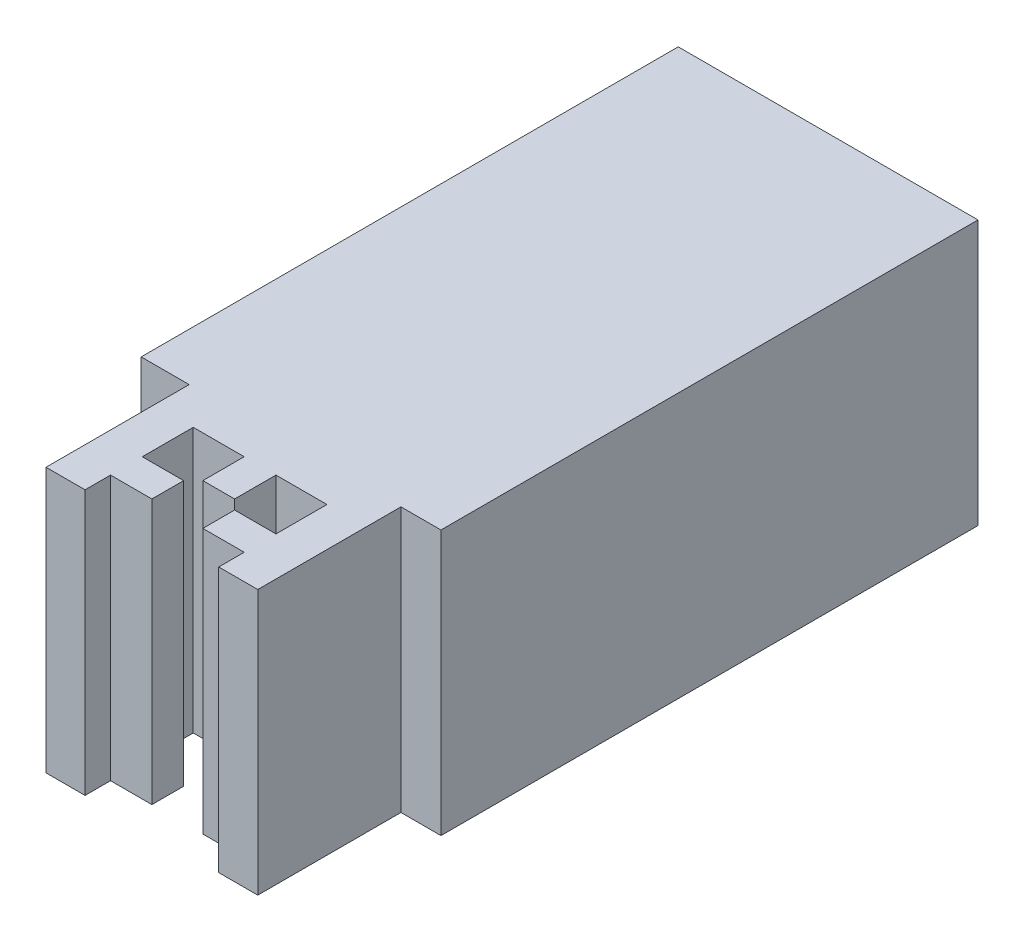
SolidWorks part; units mm, degrees
ref_plane "Plan de face" through (0, 0, 0) normal (0, 0, 1) x (1, 0, 0)
ref_plane "Plan de dessus" through (0, 0, 0) normal (0, 1, 0) x (1, 0, 0)
ref_plane "Plan de droite" through (0, 0, 0) normal (1, 0, 0) x (0, 0, -1)
sketch "Base" plane through (0, 0, 0) normal (0, 1, 0) x (1, 0, 0)
  line L0 (-3.85, -2.4) -> (-3.85, 2.4)
  line L1 (-3.85, 2.4) -> (-10.1, 2.4)
  line L2 (-10.1, 2.4) -> (-10.1, 10.1)
  line L3 (-10.1, 10.1) -> (-2.4, 10.1)
  line L4 (-2.4, 10.1) -> (-2.4, 3.85)
  line L5 (-2.4, 3.85) -> (2.4, 3.85)
  line L6 (0, -16.94) -> (0, 16.94) construction
  line L7 (2.4, 10.1) -> (2.4, 3.85)
  line L8 (10.1, 10.1) -> (2.4, 10.1)
  line L9 (10.1, 2.4) -> (10.1, 10.1)
  line L10 (3.85, 2.4) -> (10.1, 2.4)
  line L11 (3.85, -2.4) -> (3.85, 2.4)
  line L12 (-16.94, 0) -> (16.94, 0) construction
  line L13 (3.85, -2.4) -> (10.1, -2.4)
  line L14 (10.1, -2.4) -> (10.1, -6.25)
  line L20 (-10.1, -2.4) -> (-10.1, -6.25)
  line L21 (-3.85, -2.4) -> (-10.1, -2.4)
  line L23 (-15.4, 15.4) -> (15.4, 15.4)
  line L24 (-15.4, 15.4) -> (-15.4, -6.25)
  line L26 (15.4, 15.4) -> (15.4, -6.25)
  line L27 (-15.4, 15.4) -> (0, 0) construction
  line L28 (0, 0) -> (15.4, 15.4) construction
  line L29 (-10.1, -6.25) -> (-15.4, -6.25)
  line L30 (10.1, -6.25) -> (15.4, -6.25)
  line L31 (10.1, -10.1) -> (15.4, -15.4) construction
  point P2 (-3.85, 0)
  point P3 (0, 3.85)
  point P27 (0, 0)
  dimension "D1" = 4.8
  dimension "D2" = 4.8
  dimension "D3" = 6.25
  dimension "D4" = 7.7
  dimension "D5" = 30.8
extrude "Boss.-Extru.1" add sketch "Base" along normal mid plane 40
sketch "Esquisse6" plane through (0, 0, 0) normal (0, 0, 1) x (1, 0, 0)
  line L0 (10.1, 20) -> (10.1, -20) construction
  line L1 (-10.1, 10) -> (10.1, 10)
  line L2 (-10.1, 10) -> (-10.1, -10)
  line L3 (-10.1, -10) -> (10.1, -10)
  line L4 (10.1, 10) -> (10.1, -10)
  line L5 (-10.1, 10) -> (10.1, -10) construction
  line L6 (-10.1, -10) -> (10.1, 10) construction
  point P0 (0, 0)
  dimension "D1" = 20
extrude "Enlèv. mat.-Extru.1" cut sketch "Esquisse6" against normal mid plane 6
sketch "Esquisse14" plane through (0, -20, 0) normal (0, -1, 0) x (1, 0, 0)
  line L0 (15.4, 6.25) -> (15.4, -15.4) construction
  line L1 (-15.4, -15.4) -> (15.4, -15.4)
  line L2 (-15.4, -15.4) -> (-15.4, -17.9)
  line L3 (-15.4, -17.9) -> (15.4, -17.9)
  line L4 (15.4, -15.4) -> (15.4, -17.9)
  dimension "D1" = 2.5
extrude "Boss.-Extru.3" add sketch "Esquisse14" against normal up to vertex (40 mm away)
chamfer "Chanfrein1" distance 6.25 angle 45 2 edges at (3.85, -10, 0) (-3.85, -10, 0)
sketch "Esquisse16" plane through (15.4, 0, 0) normal (1, 0, 0) x (0, 0, -1)
  line L0 (-6.25, -20) -> (17.9, -20) construction
  line L1 (-6.25, 20) -> (17.9, 20)
  line L2 (-6.25, 20) -> (-6.25, -20)
  line L3 (-6.25, -20) -> (17.9, -20)
  line L4 (17.9, 20) -> (17.9, -20)
  line L5 (17.9, 20) -> (17.9, -20) construction
  line L6 (-6.25, 20) -> (-6.25, -20) construction
  dimension "D1" = 0
  dimension "D2" = 0
  dimension "D3" = 0
  dimension "D4" = 0
extrude "Boss.-Extru.4" add sketch "Esquisse16" along normal blind 40
sketch "Esquisse17" plane through (0, 0, -17.9) normal (0, 0, -1) x (-1, 0, 0)
  line L0 (15.4, 20) -> (-55.4, 20) construction
  circle A0 centre (-34.1338, 0) radius 17.5
  dimension "D1" = 20
sketch "Esquisse18" plane through (0, 0, 6.25) normal (0, 0, 1) x (1, 0, 0)
  line L0 (10.1, 20) -> (55.4, 20) construction
  line L1 (10.1, 20) -> (55.4, 20)
  line L2 (10.1, 20) -> (10.1, -20)
  line L3 (10.1, -20) -> (55.4, -20)
  line L4 (55.4, 20) -> (55.4, -20)
  line L5 (55.4, 20) -> (55.4, -20) construction
  line L6 (10.1, -20) -> (55.4, -20) construction
  line L7 (10.1, 20) -> (10.1, -20) construction
  dimension "D1" = 0
  dimension "D2" = 0
  dimension "D3" = 0
  dimension "D4" = 0
extrude "Boss.-Extru.5" add sketch "Esquisse18" along normal blind 47
extrude "Enlèv. mat.-Extru.4" cut sketch "Esquisse17" against normal blind 86
sketch "Esquisse19" plane through (0, -20, 0) normal (0, -1, 0) x (-1, 0, 0)
  line L0 (-10.1, -2.4) -> (-10.1, -53.25) construction
  line L1 (-29.1, -53.25) -> (-39.1, -53.25)
  line L2 (-29.1, -53.25) -> (-29.1, 19.3245)
  line L3 (-29.1, 19.3245) -> (-39.1, 19.3245)
  line L4 (-39.1, -53.25) -> (-39.1, 19.3245)
  line L5 (-10.1, -53.25) -> (-55.4, -53.25) construction
  dimension "D2" = 10
  dimension "D3" = 19
  dimension "D4" = 0
extrude "Enlèv. mat.-Extru.5" cut sketch "Esquisse19" against normal blind 6
sketch "Esquisse22" plane through (10.1, 0, 0) normal (-1, 0, 0) x (0, 0, 1)
  line L0 (2.4, 20) -> (53.25, 20) construction
  circle A0 centre (39.6977, 0) radius 4
  dimension "D1" = 20
extrude "Enlèv. mat.-Extru.6" cut sketch "Esquisse22" against normal blind 1 contours A0
sketch "Esquisse23" plane through (11.1, 0, 0) normal (-1, 0, 0) x (0, 0, 1)
  circle A0 centre (39.6977, 0) radius 1.25
  circle A2 centre (39.6977, 0) radius 4 construction
  dimension "D1" = 0
extrude "Enlèv. mat.-Extru.7" cut sketch "Esquisse23" against normal blind 7 contours A0
chamfer "Chanfrein4" distance 0.25 angle 45 1 edges at (11.1, 0, 40.9477)
sketch "Esquisse54" plane through (10.1, 0, 0) normal (-1, 0, 0) x (0, 0, 1)
  circle A0 centre (39.6977, 0) radius 1.6
curve "Hélice/Spirale1" pitch 0.5 height 10 turns 20
sketch "Esquisse55" plane through (0, 0, 0) normal (0, 1, 0) x (1, 0, 0)
  line L0 (14.9838, -38.4485) -> (14.5912, -38.4485)
  line L1 (14.5912, -38.4485) -> (14.7847, -38.1985)
  line L2 (14.7847, -38.1985) -> (14.9838, -38.4485)
  line L3 (14.7847, -38.1985) -> (14.7847, -38.4485)
  spline S0 degree 3 poles (10.1, -38.5663) (10.1104, -38.7135) (10.1313, -39.0699) (10.1625, -39.6976) (10.1938, -40.326) (10.225, -40.8585) (10.2563, -41.2144) (10.2875, -41.3393) (10.3188, -41.2144) (10.35, -40.8585) (10.3917, -40.1484) (10.4333, -39.247) (10.475, -38.5369) (10.5063, -38.181) (10.5375, -38.056) (10.5688, -38.181) (10.6, -38.5369) (10.6417, -39.247) (10.6833, -40.1484) (10.725, -40.8585) (10.7562, -41.2144) (10.7875, -41.3393) (10.8187, -41.2144) (10.85, -40.8585) (10.8917, -40.1484) (10.9333, -39.247) (10.975, -38.5369) (11.0063, -38.181) (11.0375, -38.056) (11.0687, -38.181) (11.1, -38.5369) (11.1417, -39.247) (11.1833, -40.1484) (11.225, -40.8585) (11.2563, -41.2144) (11.2875, -41.3393) (11.3188, -41.2144) (11.35, -40.8585) (11.3917, -40.1484) (11.4333, -39.247) (11.475, -38.5369) (11.5062, -38.181) (11.5375, -38.056) (11.5688, -38.181) (11.6, -38.5369) (11.6417, -39.247) (11.6833, -40.1484) (11.725, -40.8585) (11.7562, -41.2144) (11.7875, -41.3393) (11.8188, -41.2144) (11.85, -40.8585) (11.8917, -40.1484) (11.9333, -39.247) (11.975, -38.5369) (12.0063, -38.181) (12.0375, -38.056) (12.0688, -38.181) (12.1, -38.5369) (12.1417, -39.247) (12.1833, -40.1484) (12.225, -40.8585) (12.2563, -41.2144) (12.2875, -41.3393) (12.3187, -41.2144) (12.35, -40.8585) (12.3917, -40.1484) (12.4333, -39.247) (12.475, -38.5369) (12.5063, -38.181) (12.5375, -38.056) (12.5688, -38.181) (12.6, -38.5369) (12.6417, -39.247) (12.6833, -40.1484) (12.725, -40.8585) (12.7563, -41.2144) (12.7875, -41.3393) (12.8188, -41.2144) (12.85, -40.8585) (12.8917, -40.1484) (12.9333, -39.247) (12.975, -38.5369) (13.0063, -38.181) (13.0375, -38.056) (13.0688, -38.181) (13.1, -38.5369) (13.1417, -39.247) (13.1833, -40.1484) (13.225, -40.8585) (13.2563, -41.2144) (13.2875, -41.3393) (13.3188, -41.2144) (13.35, -40.8585) (13.3917, -40.1484) (13.4333, -39.247) (13.475, -38.5369) (13.5063, -38.181) (13.5375, -38.056) (13.5688, -38.181) (13.6, -38.5369) (13.6417, -39.247) (13.6833, -40.1484) (13.725, -40.8585) (13.7563, -41.2144) (13.7875, -41.3393) (13.8188, -41.2144) (13.85, -40.8585) (13.8917, -40.1484) (13.9333, -39.247) (13.975, -38.5369) (14.0063, -38.181) (14.0375, -38.056) (14.0688, -38.181) (14.1, -38.5369) (14.1417, -39.247) (14.1833, -40.1484) (14.225, -40.8585) (14.2563, -41.2144) (14.2875, -41.3393) (14.3187, -41.2144) (14.35, -40.8585) (14.3917, -40.1484) (14.4333, -39.247) (14.475, -38.5369) (14.5062, -38.181) (14.5375, -38.056) (14.5688, -38.181) (14.6, -38.5369) (14.6417, -39.247) (14.6833, -40.1484) (14.725, -40.8585) (14.7562, -41.2144) (14.7875, -41.3393) (14.8188, -41.2144) (14.85, -40.8585) (14.8917, -40.1484) (14.9333, -39.247) (14.975, -38.5369) (15.0063, -38.181) (15.0375, -38.056) (15.0688, -38.181) (15.1, -38.5369) (15.1417, -39.247) (15.1833, -40.1484) (15.225, -40.8585) (15.2563, -41.2144) (15.2875, -41.3393) (15.3187, -41.2144) (15.35, -40.8585) (15.3917, -40.1484) (15.4333, -39.247) (15.475, -38.5369) (15.5063, -38.181) (15.5375, -38.056) (15.5688, -38.181) (15.6, -38.5369) (15.6417, -39.247) (15.6833, -40.1484) (15.725, -40.8585) (15.7563, -41.2144) (15.7875, -41.3393) (15.8188, -41.2144) (15.85, -40.8585) (15.8917, -40.1484) (15.9333, -39.247) (15.975, -38.5369) (16.0063, -38.181) (16.0375, -38.056) (16.0688, -38.181) (16.1, -38.5369) (16.1417, -39.247) (16.1833, -40.1484) (16.225, -40.8585) (16.2563, -41.2144) (16.2875, -41.3393) (16.3188, -41.2144) (16.35, -40.8585) (16.3917, -40.1484) (16.4333, -39.247) (16.475, -38.5369) (16.5063, -38.181) (16.5375, -38.056) (16.5688, -38.181) (16.6, -38.5369) (16.6417, -39.247) (16.6833, -40.1484) (16.725, -40.8585) (16.7563, -41.2144) (16.7875, -41.3393) (16.8188, -41.2144) (16.85, -40.8585) (16.8917, -40.1484) (16.9333, -39.247) (16.975, -38.5369) (17.0063, -38.181) (17.0375, -38.056) (17.0688, -38.181) (17.1, -38.5369) (17.1417, -39.247) (17.1833, -40.1484) (17.225, -40.8585) (17.2563, -41.2144) (17.2875, -41.3393) (17.3188, -41.2144) (17.35, -40.8585) (17.3917, -40.1484) (17.4333, -39.247) (17.475, -38.5369) (17.5063, -38.181) (17.5375, -38.056) (17.5688, -38.181) (17.6, -38.5369) (17.6417, -39.247) (17.6833, -40.1484) (17.725, -40.8585) (17.7563, -41.2144) (17.7875, -41.3393) (17.8188, -41.2144) (17.85, -40.8585) (17.8917, -40.1484) (17.9333, -39.247) (17.975, -38.5369) (18.0063, -38.181) (18.0375, -38.056) (18.0688, -38.181) (18.1, -38.5369) (18.1417, -39.247) (18.1833, -40.1484) (18.225, -40.8585) (18.2563, -41.2144) (18.2875, -41.3393) (18.3188, -41.2144) (18.35, -40.8585) (18.3917, -40.1484) (18.4333, -39.247) (18.475, -38.5369) (18.5063, -38.181) (18.5375, -38.056) (18.5688, -38.181) (18.6, -38.5369) (18.6417, -39.247) (18.6833, -40.1484) (18.725, -40.8585) (18.7563, -41.2144) (18.7875, -41.3393) (18.8188, -41.2144) (18.85, -40.8585) (18.8917, -40.1484) (18.9333, -39.247) (18.975, -38.5369) (19.0063, -38.181) (19.0375, -38.056) (19.0688, -38.181) (19.1, -38.5369) (19.1417, -39.247) (19.1833, -40.1484) (19.225, -40.8585) (19.2563, -41.2144) (19.2875, -41.3393) (19.3188, -41.2144) (19.35, -40.8585) (19.3917, -40.1484) (19.4333, -39.247) (19.475, -38.5369) (19.5063, -38.181) (19.5375, -38.056) (19.5687, -38.181) (19.6, -38.5369) (19.6417, -39.247) (19.6833, -40.1484) (19.725, -40.8585) (19.7562, -41.2144) (19.7875, -41.3393) (19.8187, -41.2144) (19.85, -40.8585) (19.8917, -40.1484) (19.9333, -39.247) (19.975, -38.5369) (20.0062, -38.181) (20.0375, -38.0562) (20.0687, -38.1806) (20.0896, -38.4192) (20.1, -38.5663) knots 0 0 0 0 0.003125 0.00625 0.009375 0.0125 0.015625 0.01875 0.021875 0.025 0.028125 0.034375 0.0375 0.040625 0.04375 0.046875 0.05 0.053125 0.059375 0.0625 0.065625 0.06875 0.071875 0.075 0.078125 0.084375 0.0875 0.090625 0.09375 0.096875 0.1 0.103125 0.109375 0.1125 0.115625 0.11875 0.121875 0.125 0.128125 0.134375 0.1375 0.140625 0.14375 0.146875 0.15 0.153125 0.159375 0.1625 0.165625 0.16875 0.171875 0.175 0.178125 0.184375 0.1875 0.190625 0.19375 0.196875 0.2 0.203125 0.209375 0.2125 0.215625 0.21875 0.221875 0.225 0.228125 0.234375 0.2375 0.240625 0.24375 0.246875 0.25 0.253125 0.259375 0.2625 0.265625 0.26875 0.271875 0.275 0.278125 0.284375 0.2875 0.290625 0.29375 0.296875 0.3 0.303125 0.309375 0.3125 0.315625 0.31875 0.321875 0.325 0.328125 0.334375 0.3375 0.340625 0.34375 0.346875 0.35 0.353125 0.359375 0.3625 0.365625 0.36875 0.371875 0.375 0.378125 0.384375 0.3875 0.390625 0.39375 0.396875 0.4 0.403125 0.409375 0.4125 0.415625 0.41875 0.421875 0.425 0.428125 0.434375 0.4375 0.440625 0.44375 0.446875 0.45 0.453125 0.459375 0.4625 0.465625 0.46875 0.471875 0.475 0.478125 0.484375 0.4875 0.490625 0.49375 0.496875 0.5 0.503125 0.509375 0.5125 0.515625 0.51875 0.521875 0.525 0.528125 0.534375 0.5375 0.540625 0.54375 0.546875 0.55 0.553125 0.559375 0.5625 0.565625 0.56875 0.571875 0.575 0.578125 0.584375 0.5875 0.590625 0.59375 0.596875 0.6 0.603125 0.609375 0.6125 0.615625 0.61875 0.621875 0.625 0.628125 0.634375 0.6375 0.640625 0.64375 0.646875 0.65 0.653125 0.659375 0.6625 0.665625 0.66875 0.671875 0.675 0.678125 0.684375 0.6875 0.690625 0.69375 0.696875 0.7 0.703125 0.709375 0.7125 0.715625 0.71875 0.721875 0.725 0.728125 0.734375 0.7375 0.740625 0.74375 0.746875 0.75 0.753125 0.759375 0.7625 0.765625 0.76875 0.771875 0.775 0.778125 0.784375 0.7875 0.790625 0.79375 0.796875 0.8 0.803125 0.809375 0.8125 0.815625 0.81875 0.821875 0.825 0.828125 0.834375 0.8375 0.840625 0.84375 0.846875 0.85 0.853125 0.859375 0.8625 0.865625 0.86875 0.871875 0.875 0.878125 0.884375 0.8875 0.890625 0.89375 0.896875 0.9 0.903125 0.909375 0.9125 0.915625 0.91875 0.921875 0.925 0.928125 0.934375 0.9375 0.940625 0.94375 0.946875 0.95 0.953125 0.959375 0.9625 0.965625 0.96875 0.971875 0.975 0.978125 0.984375 0.9875 0.990625 0.99375 0.996875 1 1 1 1 construction
  dimension "D1" = 0.25
sweep "Enlèvement de matière-Balayage1" cut profiles "Esquisse55" path "Hélice/Spirale1"
sketch "Esquisse56" plane through (0, 0, 53.25) normal (0, 0, 1) x (1, 0, 0)
  line L1 (10.1, 20) -> (55.4, 20)
  line L2 (10.1, 20) -> (10.1, -20)
  line L3 (10.1, -20) -> (55.4, -20)
  line L4 (55.4, 20) -> (55.4, -20)
extrude "Boss.-Extru.6" add sketch "Esquisse56" along normal blind 10
sketch "Esquisse60" plane through (0, 20, 0) normal (0, 1, 0) x (1, 0, 0)
  line L0 (29.5, -81.0333) -> (29.5, -76.2333)
  line L1 (29.5, -76.2333) -> (23.25, -76.2333)
  line L2 (23.25, -76.2333) -> (23.25, -68.5333)
  line L3 (23.25, -68.5333) -> (30.95, -68.5333)
  line L4 (30.95, -68.5333) -> (30.95, -74.7833)
  line L5 (30.95, -74.7833) -> (35.75, -74.7833)
  line L6 (35.75, -68.5333) -> (35.75, -74.7833)
  line L7 (43.45, -68.5333) -> (35.75, -68.5333)
  line L8 (43.45, -76.2333) -> (43.45, -68.5333)
  line L9 (37.2, -76.2333) -> (43.45, -76.2333)
  line L10 (37.2, -81.0333) -> (37.2, -76.2333)
  line L11 (37.2, -81.0333) -> (43.45, -81.0333)
  line L12 (43.45, -81.0333) -> (43.45, -84.8833)
  line L13 (23.25, -81.0333) -> (23.25, -84.8833)
  line L14 (29.5, -81.0333) -> (23.25, -81.0333)
  line L15 (17.35, -62.6333) -> (49.35, -62.6333)
  line L16 (17.35, -62.6333) -> (17.35, -84.8833)
  line L17 (49.35, -62.6333) -> (49.35, -84.8833)
  line L18 (17.35, -62.6333) -> (33.35, -78.6333) construction
  line L19 (33.35, -78.6333) -> (49.35, -62.6333) construction
  line L20 (23.25, -84.8833) -> (17.35, -84.8833)
  line L21 (43.45, -84.8833) -> (49.35, -84.8833)
  line L22 (10.1, -2.4) -> (10.1, -63.25) construction
  point P19 (33.35, -78.6333)
  dimension "D1" = 4.8
  dimension "D2" = 4.8
  dimension "D3" = 6.25
  dimension "D4" = 7.7
  dimension "D5" = 7.25
extrude "Boss.-Extru.8" add sketch "Esquisse60" against normal blind 40
sketch "Esquisse61" plane through (-15.4, 0, 0) normal (-1, 0, 0) x (0, 0, 1)
  line L1 (-17.9, 20) -> (6.25, 20)
  line L2 (-17.9, 20) -> (-17.9, -20)
  line L3 (-17.9, -20) -> (6.25, -20)
  line L4 (6.25, 20) -> (6.25, -20)
extrude "Enlèv. mat.-Extru.8" cut sketch "Esquisse61" against normal blind 25.5
sketch "Esquisse63" plane through (0, 0, -17.9) normal (0, 0, -1) x (-1, 0, 0)
  circle A0 centre (-34.1338, 0) radius 18
extrude "Enlèv. mat.-Extru.9" cut sketch "Esquisse63" against normal blind 25
